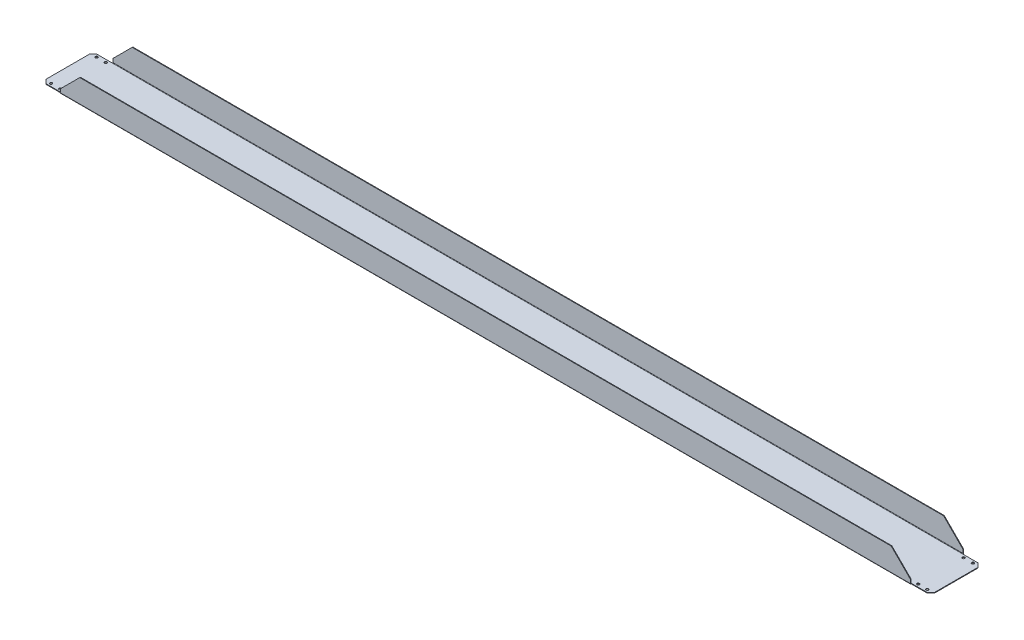
SolidWorks part; units mm, degrees
note: The reader was unsure of these and kept them because the rebuilt part matched: flange length of "邊線-凸緣1".
ref_plane "前基準面" through (0, 0, 0) normal (0, 0, 1) x (1, 0, 0)
ref_plane "上基準面" through (0, 0, 0) normal (0, 1, 0) x (1, 0, 0)
ref_plane "右基準面" through (0, 0, 0) normal (1, 0, 0) x (0, 0, -1)
sketch "草圖1" plane through (0, 0, 0) normal (0, 1, 0) x (1, 0, 0)
  line L0 (0, 107.6226) -> (0, 0) construction
  line L1 (-1150, 66) -> (-1150, -66)
  line L2 (1150, 66) -> (1150, -66)
  line L7 (-1150, -66) -> (1150, -66)
  line L11 (-1150, 66) -> (1150, 66)
  line L13 (0, 0) -> (280.3973, 0) construction
  dimension "D1" = 132
  dimension "D4" = 2300
sheet metal parameters "鈑金1" thickness 1.6 parameters "D1"=1
base flange "基材-凸緣1" sketch "草圖1" thickness 1.6 reverse thickness direction yes parameters "D1"=1
edge flange "邊線-凸緣1" sketch "草圖11" flange profiles "草圖11", "草圖12" flange angle 90 flange length 60 flange position bend outside bend radius 1 thickness 1.6 relief rectangular parameters "D6"=10, "D8"=1
bend "邊線彎折3" bend radius 1 bend angle 90 parameters "D5"=1
bend "邊線彎折4" bend radius 1 bend angle 90 parameters "D5"=2
sketch "草圖11" plane through (0, 1.6, -66) normal (0, 0, -1) x (-1, 0, 0)
  line L0 (-1150, 0) -> (1150, 0) construction
  line L1 (-1100, 0) -> (1100, 0)
  line L2 (-1100, 0) -> (-1100, 60)
  line L3 (-1100, 60) -> (1100, 60)
  line L4 (1100, 60) -> (1100, 0)
  dimension "D1" = 50
  dimension "D2" = 50
sketch "草圖12" plane through (0, 1.6, 66) normal (0, 0, 1) x (1, 0, 0)
  line L0 (-1150, 0) -> (1150, 0) construction
  line L1 (-1100, 0) -> (1100, 0)
  line L2 (-1100, 0) -> (-1100, 60)
  line L3 (-1100, 60) -> (1100, 60)
  line L4 (1100, 60) -> (1100, 0)
  line L5 (-1100, 60) -> (-1100, 0) construction
  line L6 (1100, 0) -> (1100, 60) construction
hole_wizard "Ø6.4 (6.4) 直徑孔1" positions "草圖16" profile "草圖15" hole size "Ø6.4" standard "ISO"
sketch "草圖16" plane through (0, 1.6, 0) normal (0, 1, 0) x (-1, 0, 0)
  line L0 (-1150, 0) -> (-674.9736, 0) construction
  line L1 (-1150, 66) -> (-1150, -66) construction
  line L3 (1150, -66) -> (1150, 66) construction
  point P0 (1110, -59)
  point P1 (1134, -59)
  point P3 (1134, 59)
  point P5 (1110, 59)
  point P7 (-1110, -59)
  point P9 (-1134, -59)
  point P11 (-1110, 59)
  point P13 (-1134, 59)
  dimension "D1" = 24
  dimension "D2" = 16
  dimension "D3" = 118
  dimension "D4" = 16
  dimension "D5" = 24
sketch "草圖15" plane through (-1110, 1.6, -59) normal (1, 0, 0) x (0, 0, 1)
  line L0 (0, 0) -> (0, 2)
  line L1 (0, 2) -> (3.2, 2)
  line L2 (3.2, 2) -> (3.2, 0)
  line L5 (3.2, 0) -> (0, 0)
  line L10 (0, 2) -> (-3.2, 2) construction
  line L11 (0, -6.35) -> (0, 107.95) construction
  dimension "鑽孔直徑" = 6.4
  dimension "鑽孔深度" = 2
  dimension "導頭角度" = 180
chamfer "導角1" distance 50 angle 45 4 edges at (-1100, 61.6, 67.8) (-1100, 61.6, -67.8) (1100, 61.6, -67.8) (1100, 61.6, 67.8)
chamfer "導角3" distance 10 angle 45 4 edges at (-1150, 0.8, 66) (-1150, 0.8, -66) (1150, 0.8, -66) (1150, 0.8, 66)
flat pattern "平板-型式1" [suppressed]
sketch "彎折-線1" plane through (0, 0, 0) normal (0, 1, 0) x (-1, 0, 0)
bend of the flat pattern "平板-<邊線彎折3>1"
bend of the flat pattern "平板-<邊線彎折4>1"
